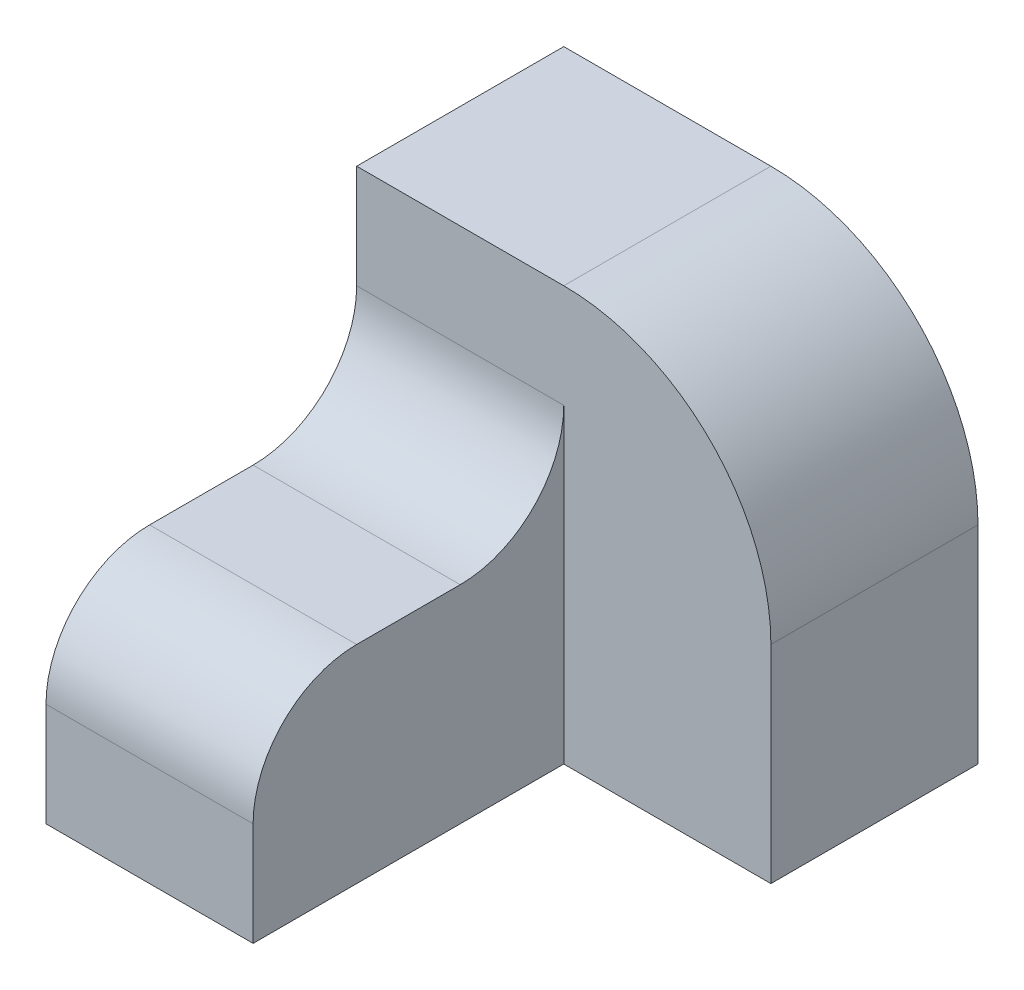
SolidWorks part; units mm, degrees
ref_plane "前基準面" through (0, 0, 0) normal (0, 0, 1) x (1, 0, 0)
ref_plane "上基準面" through (0, 0, 0) normal (0, 1, 0) x (1, 0, 0)
ref_plane "右基準面" through (0, 0, 0) normal (1, 0, 0) x (0, 0, -1)
sketch "草圖1" plane through (0, 0, 0) normal (0, 1, 0) x (1, 0, 0)
  line L1 (0, 0) -> (10, 0)
  line L2 (0, 0) -> (0, -15)
  line L3 (0, -15) -> (10, -15)
  line L4 (10, 0) -> (10, -15)
  line L5 (0, 0) -> (20, 0)
  line L6 (0, 0) -> (0, 10)
  line L7 (0, 10) -> (20, 10)
  line L8 (20, 0) -> (20, 10)
  dimension "D1" = 10
  dimension "D2" = 10
  dimension "D3" = 20
  dimension "D4" = 15
extrude "填料-伸長1" add sketch "草圖1" along normal blind 10 contours L4 L1 L2 L3 region at (5, 0, 7.5)
extrude "填料-伸長2" add sketch "草圖1<3>" along normal blind 20 contours L5 L8 L7 L6 L1 region at (10, 0, -5)
sketch "草圖1<3>" plane through (0, 0, 0) normal (0, 1, 0) x (1, 0, 0) same geometry as "草圖1"
fillet "圓角1" radius 5 2 edges at (5, 10, 0) (5, 10, 15)
fillet "圓角2" radius 10 1 edges at (20, 20, -5)
